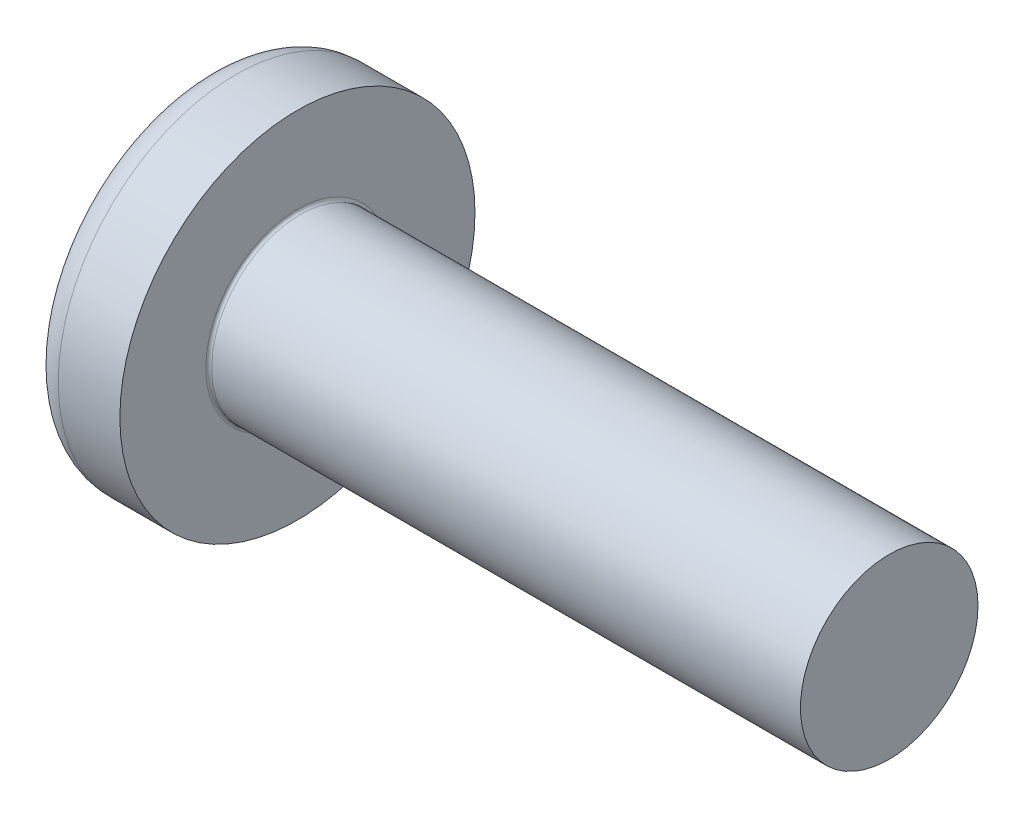
SolidWorks part; units mm, degrees
ref_plane "Front" through (0, 0, 0) normal (0, 0, 1) x (1, 0, 0)
ref_plane "Top" through (0, 0, 0) normal (0, 1, 0) x (1, 0, 0)
ref_plane "Right" through (0, 0, 0) normal (1, 0, 0) x (0, 0, -1)
sketch "Sketch1" plane through (0, 0, 0) normal (1, 0, 0) x (0, 0, -1)
  circle A0 centre (0, 0) radius 6
  dimension "dk" = 12
extrude "BaseHead" add sketch "Sketch1" along normal blind 4.6
sketch "Sketch2" plane through (4.6, 0, 0) normal (1, 0, 0) x (0, 0, -1)
  circle A0 centre (0, 0) radius 3
extrude "BaseBody" add sketch "Sketch2" along normal blind 20
cosmetic thread "ThreadCosmetic1" [suppressed] parameters "D1"=18, "THD_MINOR"=5
fillet "Fillet1" radius 0.1 1 edges at (4.6, 0, -3)
sketch "Sketch3" plane through (-4.0827, -1.9173, 0) normal (0, 0, 1) x (0, -1, 0)
  line L0 (-1.9173, 6.3195) -> (-1.9173, 20.448) construction
  line L3 (-7.9173, 4.0827) -> (-1.9173, 4.0827) construction
  line L5 (-7.9173, 6.0827) -> (-7.9173, -0.9173)
  line L6 (-1.9173, 4.0827) -> (-1.9173, -0.9173)
  line L7 (-1.9173, -0.9173) -> (-7.9173, -0.9173)
  line L8 (-7.9173, 8.6827) -> (-7.9173, 4.0827) construction
  arc A0 (-7.9173, 6.0827) -> (-1.9173, 4.0827) centre (-1.9173, 14.0827) ccw
  dimension "r1" = 10
  dimension "D2" = 5
revolve "BaseTop" cut sketch "Sketch3" angle 360 about L0
sketch "Sketch4" plane through (0, 0, 0) normal (1, 0, 0) x (0, 0, -1)
  line L1 (2.396, 0) -> (1.198, 2.075)
  line L2 (1.198, 2.075) -> (-1.198, 2.075)
  line L3 (-1.198, 2.075) -> (-2.396, 0)
  line L4 (-2.396, 0) -> (-1.198, -2.075)
  line L5 (-1.198, -2.075) -> (1.198, -2.075)
  line L6 (1.198, -2.075) -> (2.396, 0)
  circle A0 centre (0, 0) radius 2.075 construction
  dimension "B" = 4.15
extrude "Socket" cut sketch "Sketch4" along normal blind 2
sketch "Sketch5" plane through (2, 0, 0) normal (-1, 0, 0) x (0, 0, 1)
  line L0 (2.396, 0) -> (1.198, -2.075) construction
  line L1 (1.198, 2.075) -> (2.396, 0) construction
  line L2 (1.198, -2.075) -> (-1.198, -2.075) construction
  line L3 (-1.198, -2.075) -> (-2.396, 0) construction
  line L4 (-1.198, 2.075) -> (1.198, 2.075) construction
  line L5 (-2.396, 0) -> (-1.198, 2.075) construction
  line L6 (2.396, 0) -> (1.198, -2.075)
  line L7 (1.198, 2.075) -> (2.396, 0)
  line L8 (1.198, -2.075) -> (-1.198, -2.075)
  line L9 (-1.198, -2.075) -> (-2.396, 0)
  line L10 (-1.198, 2.075) -> (1.198, 2.075)
  line L11 (-2.396, 0) -> (-1.198, 2.075)
extrude "Cut-Extrude2" cut sketch "Sketch5" against normal blind 5 draft 60
sketch "Sketch6" plane through (-30.7487, 13.2487, 0) normal (0, 0, 1) x (0, -1, 0)
  line L0 (13.2487, 89.8637) -> (13.2487, 24.8312) construction
  line L1 (-4.2513, 35.3487) -> (10.6487, 35.3487)
  line L2 (-4.2513, 35.3487) -> (-4.2513, 45.3487)
  line L3 (-4.2513, 45.3487) -> (10.2487, 45.3487)
  line L4 (10.7487, 35.4487) -> (10.7487, 43.3487)
  line L5 (10.6487, 35.3487) -> (10.7487, 35.3487)
  line L6 (10.2487, 45.3487) -> (10.7487, 43.3487)
  line L7 (10.7487, 35.4487) -> (10.7487, 35.3487)
  line L8 (16.2487, 55.3487) -> (10.2487, 55.3487) construction
  line L9 (19.2487, 35.3487) -> (7.2487, 35.3487) construction
  arc A0 (10.6487, 35.3487) -> (10.7487, 35.4487) centre (10.6487, 35.4487) ccw construction
  dimension "d1" = 5
  dimension "D2" = 15
  dimension "b" = 10
  dimension "x" = 2
fillet "HeadFillet2" radius 1 1 edges at (2, 0, 6)
sketch "Sketch8" plane through (0, 0, 0) normal (0, 0, 1) x (1, 0, 0)
  line L0 (24.6, 2.567) -> (24.85, 3)
  line L1 (24.85, 3) -> (24.85, 3.5)
  line L2 (24.85, 3.5) -> (24.35, 3.5)
  line L3 (24.35, 3.5) -> (24.35, 3)
  line L4 (24.35, 3) -> (24.6, 2.567)
  line L5 (24.6, -3) -> (24.6, 3) construction
  line L6 (0, 0) -> (27.6816, 0) construction
  dimension "D1" = 0.5
  dimension "D2" = 6
revolve "Cut-Revolve10" [suppressed] cut sketch "Sketch8" angle 360 about L6
pattern_linear "LPattern10" [suppressed] count 30 spacing 0.6 along (-1, 0, 0) of bodies 107
equation "\"D2@Sketch8\" = \"d@Sketch2\""
equation "\"D1@Sketch8\" =  ( \"d@Sketch2\" - \"THD_MINOR@ThreadCosmetic1\" )  / 2"
equation "\"D3@LPattern10\" = \"D1@Sketch8\" * 1.2"
equation "\"D1@LPattern10\" = \"D1@ThreadCosmetic1\" / \"D3@LPattern10\" "
